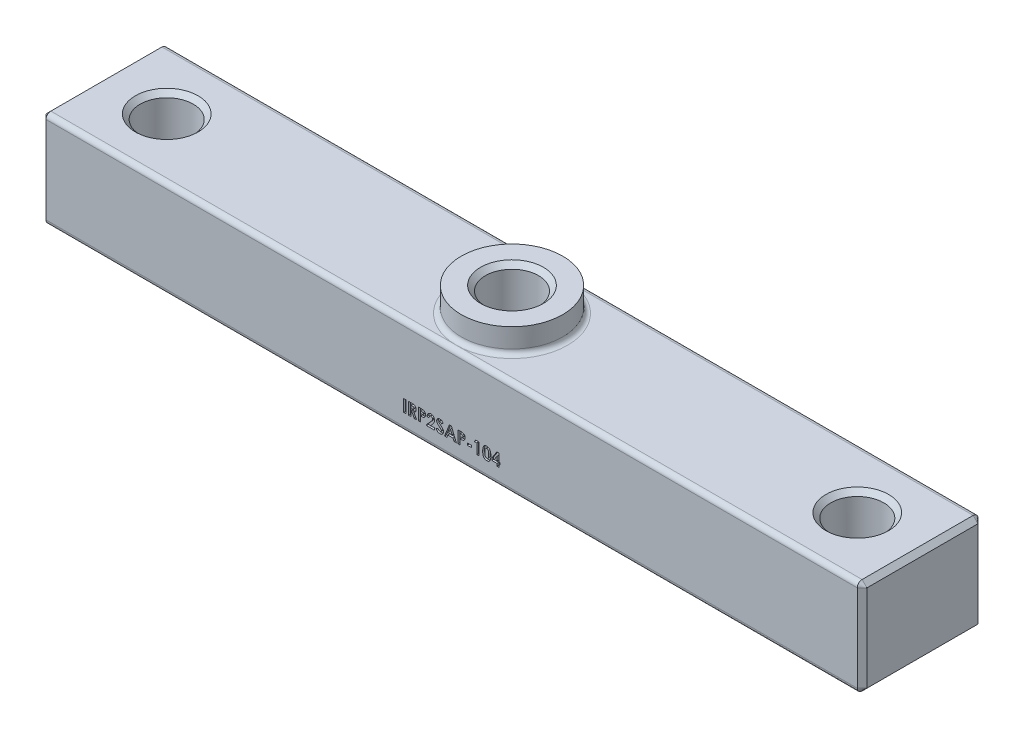
SolidWorks part; units mm, degrees
material "6061-T6 (SS)"
ref_plane "Front" through (0, 0, 0) normal (0, 0, 1) x (1, 0, 0)
ref_plane "Top" through (0, 0, 0) normal (0, 1, 0) x (1, 0, 0)
ref_plane "Right" through (0, 0, 0) normal (1, 0, 0) x (0, 0, -1)
sketch "Sketch1" plane through (0, 0, 0) normal (1, 0, 0) x (0, 0, -1)
  line L1 (0, 0) -> (31.75, 0)
  line L2 (0, 0) -> (0, 25.4)
  line L3 (0, 25.4) -> (31.75, 25.4)
  line L4 (31.75, 0) -> (31.75, 25.4)
  dimension "D1" = 31.75
  dimension "D2" = 25.4
extrude "Boss-Extrude1" add sketch "Sketch1" along normal mid plane 215.9
sketch "Sketch2" plane through (0, 25.4, 0) normal (0, 1, 0) x (1, 0, 0)
  line L0 (0, 0) -> (0, 15.875) construction
  line L1 (107.95, 0) -> (-107.95, 0) construction
  line L2 (0, 15.875) -> (0, 31.75) construction
  line L3 (107.95, 31.75) -> (-107.95, 31.75) construction
  circle A0 centre (0, 15.875) radius 13.335
  dimension "D1" = 26.67
extrude "Boss-Extrude2" add sketch "Sketch2" along normal blind 6.35
sketch "Sketch3" plane through (0, 31.75, 0) normal (0, 1, 0) x (1, 0, 0)
  line L0 (-107.95, 15.875) -> (-90.805, 15.875) construction
  line L1 (-107.95, 31.75) -> (-107.95, 0) construction
  line L2 (-90.805, 15.875) -> (0, 15.875) construction
  line L3 (0, 15.875) -> (90.805, 15.875) construction
  line L4 (90.805, 15.875) -> (107.95, 15.875) construction
  line L5 (107.95, 31.75) -> (107.95, 0) construction
  circle A0 centre (0, 15.875) radius 6.985
  circle A1 centre (-90.805, 15.875) radius 6.985
  circle A2 centre (90.805, 15.875) radius 6.985
  dimension "D1" = 13.97
  dimension "D2" = 17.145
extrude "Cut-Extrude1" cut sketch "Sketch3" against normal through all
fillet "Fillet1" radius 1.27 5 edges at (0, 0, 0) (0, 0, -31.75) (0, 25.4, -31.75) (0, 25.4, 0) (0, 25.4, -29.21)
chamfer "Chamfer1" distance 1.27 angle 45 22 edges at (90.805, 25.4, -22.86) (90.805, 0, -8.89) (0, 31.75, -8.89) (0, 0, -8.89) (-90.805, 25.4, -22.86) (-90.805, 0, -8.89) (107.95, 0, -15.875) (107.95, 0.372, -31.378) (107.95, 0.372, -0.372) (107.95, 12.7, -31.75) (107.95, 12.7, 0) (107.95, 25.028, -31.378) (107.95, 25.028, -0.372) (107.95, 25.4, -15.875) (-107.95, 0, -15.875) (-107.95, 0.372, -31.378) (-107.95, 0.372, -0.372) (-107.95, 12.7, -31.75) (-107.95, 12.7, 0) (-107.95, 25.028, -31.378) (-107.95, 25.028, -0.372) (-107.95, 25.4, -15.875)
sketch "Sketch4" plane through (0, 0, 0) normal (0, 0, 1) x (1, 0, 0)
  line L0 (-38.1, 4.445) -> (38.1, 4.445) construction
  line L1 (0, 1.27) -> (0, 4.445) construction
  line L2 (-106.68, 1.27) -> (106.68, 1.27) construction
  text T0 "<b>IRP2SAP-104</b>"
  dimension "D1" = 3.175
  dimension "D2" = 76.2
extrude "Cut-Extrude2" cut sketch "Sketch4" against normal blind 0.508
sketch "Sketch5" plane through (0, 0, -31.75) normal (0, 0, -1) x (-1, 0, 0)
  line L0 (0, 1.27) -> (0, 4.445) construction
  line L1 (-106.68, 1.27) -> (106.68, 1.27) construction
  line L2 (-38.1, 4.445) -> (38.1, 4.445) construction
  text T0 "<b>IRP2SAP-105</b>"
  dimension "D1" = 3.175
  dimension "D2" = 76.2
extrude "Cut-Extrude3" cut sketch "Sketch5" against normal blind 0.508
